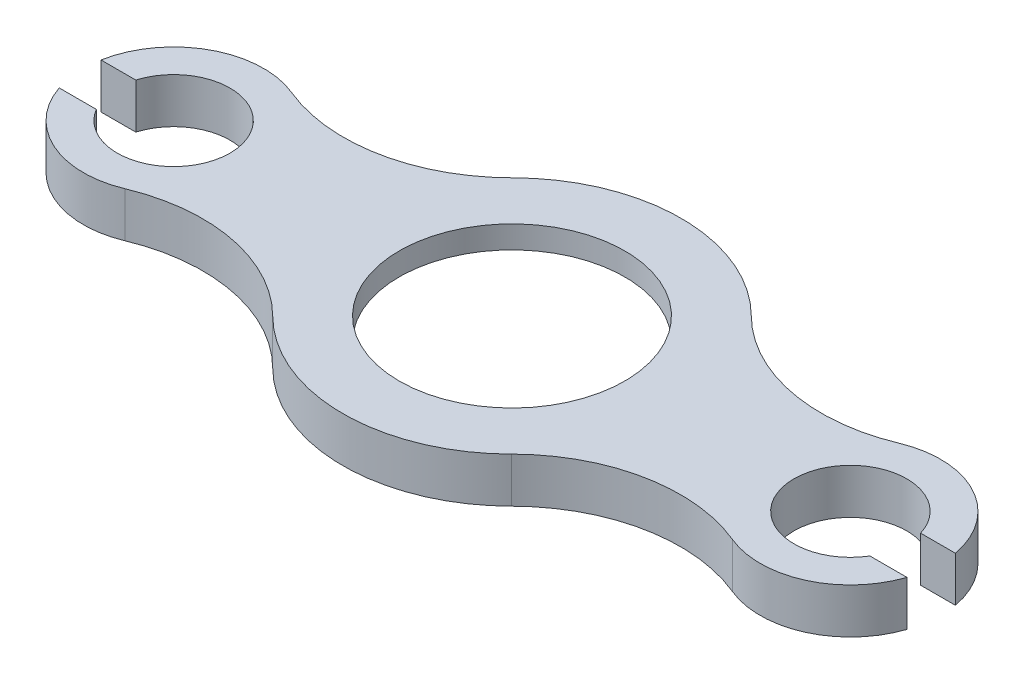
SolidWorks part; units mm, degrees
ref_plane "Front Plane" through (0, 0, 0) normal (0, 0, 1) x (1, 0, 0)
ref_plane "Top Plane" through (0, 0, 0) normal (0, 1, 0) x (1, 0, 0)
ref_plane "Right Plane" through (0, 0, 0) normal (1, 0, 0) x (0, 0, -1)
sketch "Sketch6" plane through (0, 0, 0) normal (0, 1, 0) x (1, 0, 0)
  line L0 (-209, 0) -> (209, 0) construction
  line L1 (0, -82.5) -> (0, 82.5) construction
  circle A0 centre (0, 0) radius 50
  circle A2 centre (150, 0) radius 25
  circle A3 centre (0, 0) radius 67.8
  circle A8 centre (-150, 0) radius 25
  arc A13 (-52.9583, -53.1076) -> (52.9583, -53.1076) centre (0, 0) ccw
  arc A14 (134.6667, -36.9444) -> (134.6667, 36.9444) centre (150, 0) ccw
  arc A15 (-134.6667, 36.9444) -> (-134.6667, -36.9444) centre (-150, 0) ccw
  arc A16 (52.9583, 53.1076) -> (134.6667, 36.9444) centre (105.9167, 106.2152) ccw
  arc A17 (52.9583, -53.1076) -> (134.6667, -36.9444) centre (105.9167, -106.2152) cw
  arc A18 (-52.9583, 53.1076) -> (-134.6667, 36.9444) centre (-105.9167, 106.2152) cw
  arc A19 (-52.9583, -53.1076) -> (-134.6667, -36.9444) centre (-105.9167, -106.2152) ccw
  arc A20 (52.9583, 53.1076) -> (-52.9583, 53.1076) centre (0, 0) ccw
  point P3 (0, 67.8)
  point P4 (150, 40)
  dimension "D1" = 100
  dimension "D2" = 135.6
  dimension "D4" = 50
  dimension "D5" = 150
  dimension "D6" = 80
  dimension "D8" = 75
  dimension "D3" = 150
extrude "Boss-Extrude6" add sketch "Sketch6" along normal blind 20 contours A14 A16 A20 A18 A15 A19 A13 A17 | A0 | A2 | A8
extrude "Cut-Extrude11" cut sketch "Sketch6<8>" along normal blind 10 contours A3
sketch "Sketch6<8>" plane through (0, 0, 0) normal (0, 1, 0) x (1, 0, 0) same geometry as "Sketch6"
sketch "Sketch9" plane through (0, 0, 0) normal (0, -1, 0) x (1, 0, 0)
  line L0 (0, -11) -> (0, 11) construction
  line L1 (170.6894, 12.8165) -> (191.8568, 12.8165)
  line L2 (170.6894, 12.8165) -> (170.6894, -7.1835)
  line L3 (170.6894, -7.1835) -> (191.8568, -7.1835)
  line L4 (191.8568, 12.8165) -> (191.8568, -7.1835)
  line L5 (170.6894, 12.8165) -> (191.8568, -7.1835) construction
  line L6 (170.6894, -7.1835) -> (191.8568, 12.8165) construction
  line L7 (-170.6894, -7.1835) -> (-191.8568, -7.1835)
  line L8 (-170.6894, 12.8165) -> (-170.6894, -7.1835)
  line L9 (-170.6894, 12.8165) -> (-191.8568, 12.8165)
  line L10 (-191.8568, 12.8165) -> (-191.8568, -7.1835)
  point P0 (181.2731, 2.8165)
  dimension "D1" = 20
extrude "Cut-Extrude13" cut sketch "Sketch9" against normal blind 30
